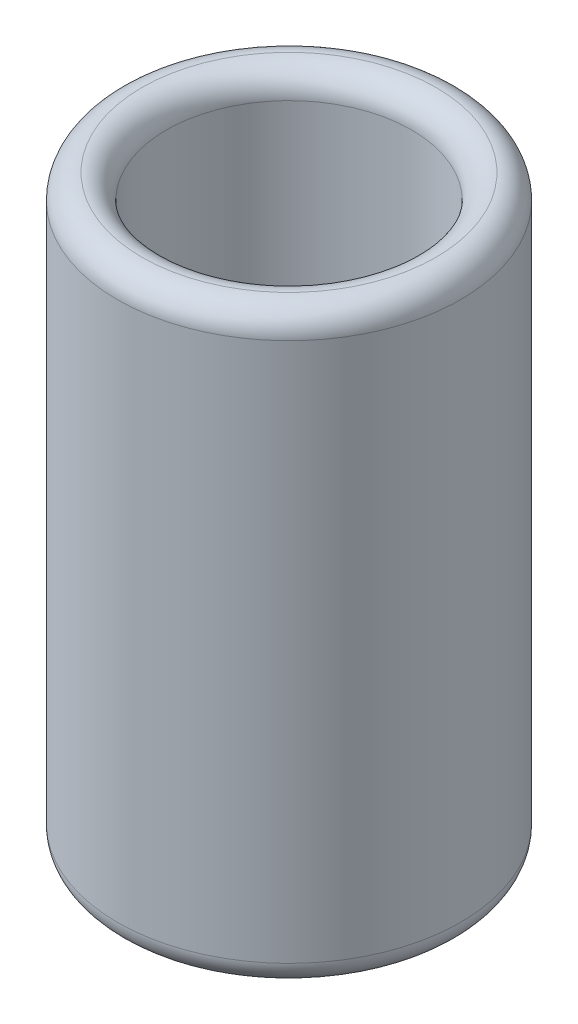
SolidWorks part; units mm, degrees
ref_plane "Front Plane" through (0, 0, 0) normal (0, 0, 1) x (1, 0, 0)
ref_plane "Top Plane" through (0, 0, 0) normal (0, 1, 0) x (1, 0, 0)
ref_plane "Right Plane" through (0, 0, 0) normal (1, 0, 0) x (0, 0, -1)
sketch "Sketch1" plane through (0, 0, 0) normal (0, 1, 0) x (1, 0, 0)
  circle A0 centre (0, 0) radius 1.25
  circle A1 centre (0, 0) radius 1.75
  dimension "D1" = 2.5
  dimension "D2" = 3.5
extrude "Boss-Extrude1" add sketch "Sketch1" along normal blind 6
fillet "Fillet1" radius 0.25 4 edges at (0, 0, 1.25) (0, 0, 1.75) (0, 6, 1.25) (0, 6, 1.75)
